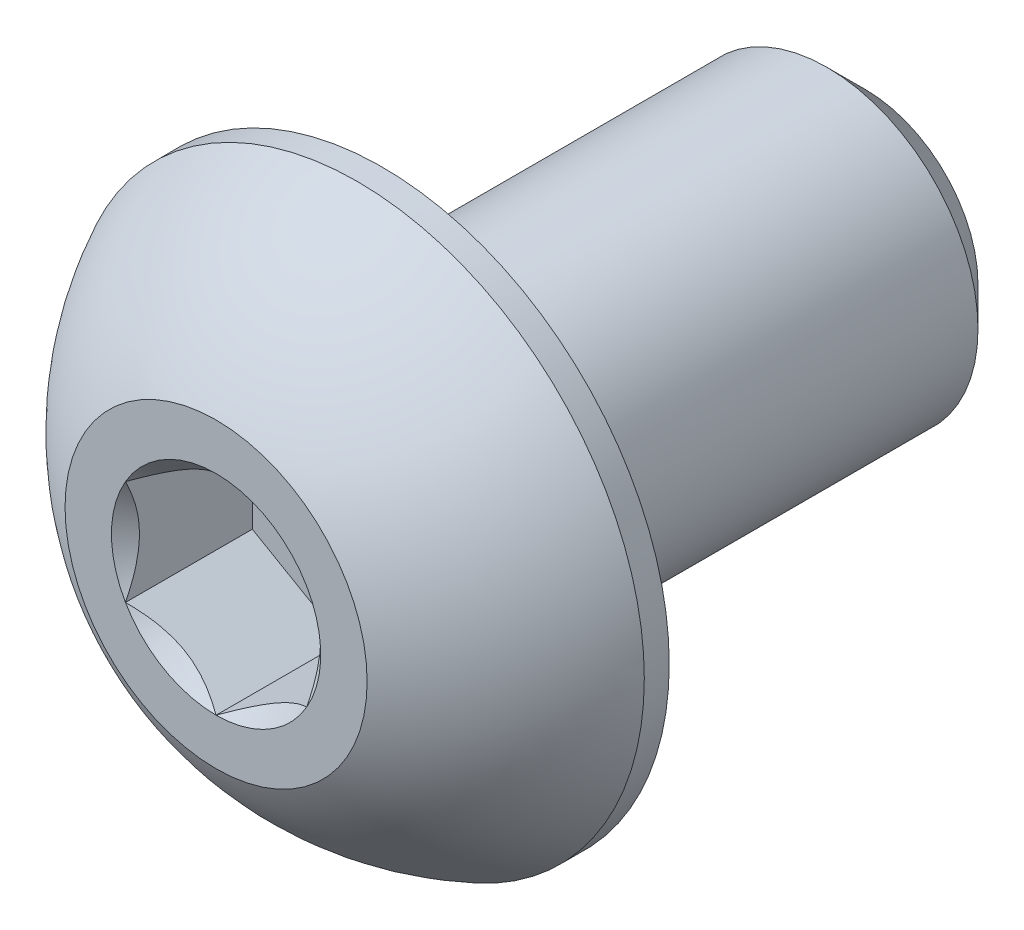
SolidWorks part; units mm, degrees
material "Alloy Steel"
ref_plane "Front Plane" through (0, 0, 0) normal (0, 0, 1) x (1, 0, 0)
ref_plane "Top Plane" through (0, 0, 0) normal (0, 1, 0) x (1, 0, 0)
ref_plane "Right Plane" through (0, 0, 0) normal (1, 0, 0) x (0, 0, -1)
sketch "Sketch1" plane through (0, 0, 0) normal (1, 0, 0) x (0, 0, -1)
  line L0 (-5.375, 0) -> (5.375, 0) construction
  line L1 (-2.625, 4.75) -> (-2.625, -4.75) construction
  line L2 (5.375, 2.5) -> (5.375, -2.5) construction
  line L3 (5.325, 2.5866) -> (5.725, 1.8938) construction
  line L4 (5.725, 1.8938) -> (6.125, 2.5866) construction
  line L5 (6.125, 2.5866) -> (5.325, 2.5866) construction
  line L6 (5.375, 2.5) -> (6.075, 2.5) construction
  line L7 (5.725, 2.5866) -> (5.725, 2.5) construction
  line L8 (5.725, 2.5) -> (5.725, 1.9804) construction
  line L9 (5.725, 1.9804) -> (5.725, 1.8938) construction
  line L10 (5.675, 1.9804) -> (5.775, 1.9804)
  line L11 (5.35, 2.5433) -> (6.1, 2.5433)
  line L12 (5.775, 1.9804) -> (6.1, 2.5433)
  line L13 (5.675, 1.9804) -> (5.35, 2.5433)
  line L14 (-5.375, 1.5) -> (-5.375, -1.5) construction
  line L15 (5.375, 2.5) -> (-2.625, 2.5) construction
  point P3 (-2.625, 0)
  point P6 (-3.275, 0)
  point P21 (5.725, 2.5433)
  point P24 (-3.0375, 4.75)
  point P25 (3.375, -2.5)
  point P26 (-5.375, 2.5)
  dimension "Head Height" = 2.75
  dimension "Length" = 8
  dimension "Head Dia" = 9.5
  dimension "Thread Dia" = 5
  dimension "Pitch" = 0.8
  dimension "D2" = 0.1
  dimension "Drive Size" = 3
  dimension "D1" = 2.1
  dimension "D3" = 0.4125
  dimension "D4" = 2
sketch "Sketch2" plane through (0, 0, 0) normal (1, 0, 0) x (0, 0, -1)
  line L0 (-5.375, 0) -> (5.375, 0)
  line L1 (5.375, 0) -> (5.375, 1.86)
  line L2 (5.375, 2.5) -> (5.375, -2.5) construction
  line L3 (5.375, 1.86) -> (4.735, 2.5)
  line L4 (4.735, 2.5) -> (-2.625, 2.5)
  line L5 (-2.625, 4.75) -> (-2.625, -4.75) construction
  line L6 (-2.625, 2.5) -> (-2.625, 4.75)
  line L7 (-2.625, 4.75) -> (-3.0375, 4.75)
  line L8 (5.375, 2.5) -> (6.075, 2.5) construction
  line L9 (-5.375, 0) -> (-5.375, 2.5)
  arc A0 (-5.375, 2.5) -> (-3.0375, 4.75) centre (-0.7169, 0) cw
  dimension "D1" = 0.64
  dimension "D2" = 45
revolve "Revolve1" add sketch "Sketch2" angle 360 about L0
sketch "Sketch3" plane through (0, 0, 5.375) normal (0, 0, 1) x (1, 0, 0)
  line L1 (0, 1.7321) -> (-1.5, 0.866)
  line L2 (-1.5, 0.866) -> (-1.5, -0.866)
  line L3 (-1.5, -0.866) -> (0, -1.7321)
  line L4 (0, -1.7321) -> (1.5, -0.866)
  line L5 (1.5, -0.866) -> (1.5, 0.866)
  line L6 (1.5, 0.866) -> (0, 1.7321)
  circle A0 centre (0, 0) radius 1.5 construction
  dimension "D1" = 3
extrude "Cut-Extrude1" cut sketch "Sketch3" against normal up to vertex (2.1 mm away) up to point (0, 0, 3.275)
sketch "Sketch4" plane through (0, 0, 5.375) normal (0, 0, 1) x (1, 0, 0)
  circle A0 centre (0, 0) radius 1.7321
extrude "Cut-Extrude2" cut sketch "Sketch4" against normal blind 10 draft 45
split "Split1" [suppressed] bodies to split 106
sketch "Sketch5" [suppressed] plane through (0, 0, -5.375) normal (0, 0, -1) x (-1, 0, 0)
  circle A0 centre (0, 0) radius 2.5 construction
  circle A1 centre (0, 0) radius 2.5
curve "Helix/Spiral1" [suppressed] pitch 0.8 height 8.8 turns 11
sketch "Sketch6" [suppressed] plane through (0, 0, 0) normal (1, 0, 0) x (0, 0, -1)
  line L0 (5.675, 1.9804) -> (5.775, 1.9804) construction
  line L1 (5.675, 1.9804) -> (5.35, 2.5433) construction
  line L2 (5.35, 2.5433) -> (6.1, 2.5433) construction
  line L3 (5.775, 1.9804) -> (6.1, 2.5433) construction
  line L4 (5.675, 1.9804) -> (5.775, 1.9804)
  line L5 (5.675, 1.9804) -> (5.35, 2.5433)
  line L6 (5.35, 2.5433) -> (6.1, 2.5433)
  line L7 (5.775, 1.9804) -> (6.1, 2.5433)
sweep "Cut-Sweep1" [suppressed] cut profiles "Sketch6" path "Helix/Spiral1"
sketch "Sketch7" [suppressed] plane through (0, 0, 2.625) normal (0, 0, -1) x (-1, 0, 0)
  circle A1 centre (0, 0) radius 2.5
  circle A2 centre (0, 0) radius 2.5
  dimension "D1" = 0
extrude "Boss-Extrude1" [suppressed] add sketch "Sketch7" along normal blind 10 draft 30
equation "\"D2@Sketch1\" = \"Pitch@Sketch1\" / 8"
equation "\"D1@Sketch1\"=\"Drive Size@Sketch1\"*.7"
equation "\"D3@Sketch1\"=\"Head Height@Sketch1\"*.15"
equation "\"D1@Sketch2\"=\"Pitch@Sketch1\"*.8"
equation "\"D1@Sketch3\"=\"Drive Size@Sketch1\""
equation "\"D4@Helix/Spiral1\"=\"Pitch@Sketch1\""
equation "\"D3@Helix/Spiral1\"=\"Length@Sketch1\"+\"Pitch@Sketch1\""
equation "\"D4@Sketch1\"=\"Pitch@Sketch1\"*2.5"
